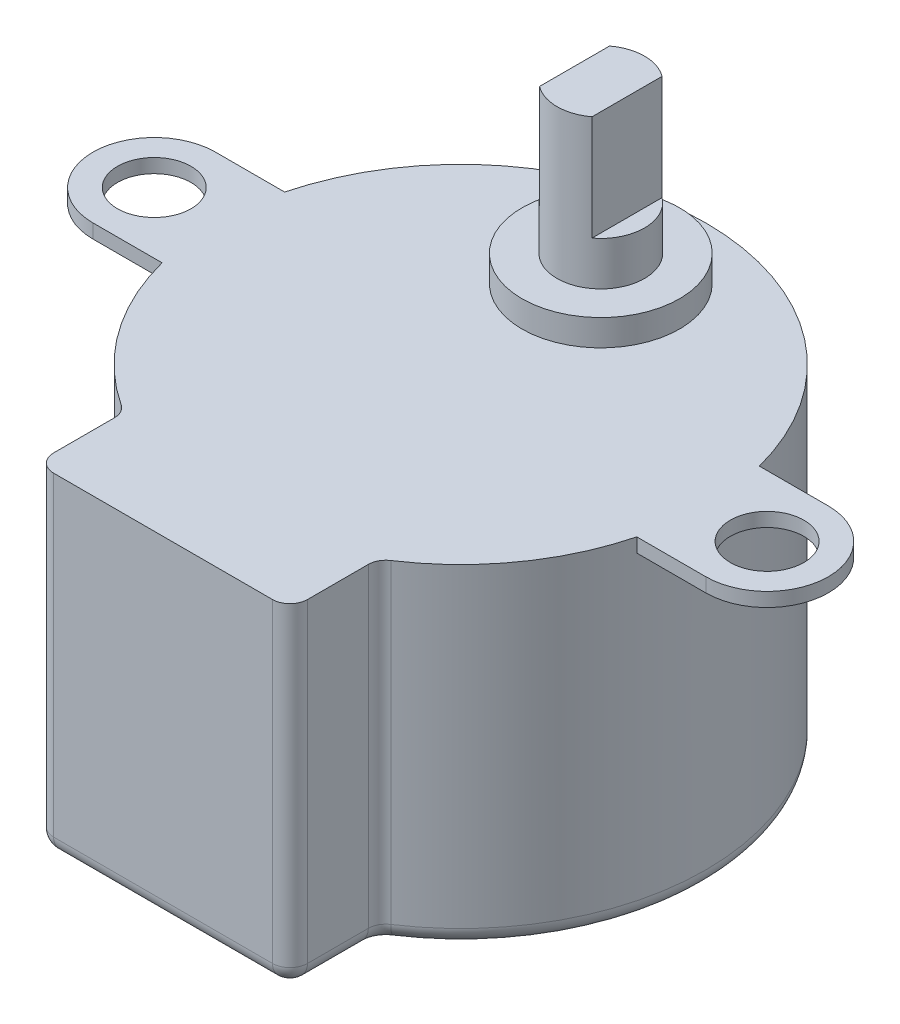
SolidWorks part; units mm, degrees
ref_plane "Front Plane" through (0, 0, 0) normal (0, 0, 1) x (1, 0, 0)
ref_plane "Top Plane" through (0, 0, 0) normal (0, 1, 0) x (1, 0, 0)
ref_plane "Right Plane" through (0, 0, 0) normal (1, 0, 0) x (0, 0, -1)
sketch "Sketch1" plane through (0, 0, 0) normal (0, 1, 0) x (1, 0, 0)
  line L1 (-7.25, 0) -> (7.25, 0)
  line L2 (-7.25, 0) -> (-7.25, -17)
  line L3 (-7.25, -17) -> (7.25, -17)
  line L4 (7.25, 0) -> (7.25, -17)
  circle A0 centre (0, 0) radius 14
  dimension "D1" = 28
  dimension "D2" = 14.5
  dimension "D3" = 7.25
  dimension "D4" = 17
extrude "Boss-Extrude1" add sketch "Sketch1" along normal blind 19 contours A0 | L3 L4 L1 L2
sketch "Sketch2" plane through (0, 19, 0) normal (0, 1, 0) x (1, 0, 0)
  line L0 (-7.25, -17) -> (7.25, -17) construction
  circle A0 centre (0, 8) radius 2.5
  circle A1 centre (0, 8) radius 4.5
  dimension "D1" = 9
  dimension "D2" = 5
  dimension "D3" = 25
extrude "Boss-Extrude2" add sketch "Sketch2" along normal blind 1.5 contours A1
extrude "Boss-Extrude3" add sketch "Sketch2<3>" along normal blind 10 contours A0
sketch "Sketch2<3>" plane through (0, 19, 0) normal (0, 1, 0) x (1, 0, 0) same geometry as "Sketch2"
sketch "Sketch3" plane through (0, 29, 0) normal (0, 1, 0) x (1, 0, 0)
  line L0 (-1.5, 10.0498) -> (-1.5, 5.9502)
  line L1 (1.5, 10.0498) -> (1.5, 5.9502)
  circle A0 centre (0, 8) radius 2.54
  circle M1 centre (0, 8) radius 2.5
  dimension "D3" = 5.08
  dimension "D1" = 3
  dimension "D2" = 1.5
extrude "Cut-Extrude1" cut sketch "Sketch3" against normal blind 6 contours L0 M1 | L1 M1 region at (-1.9078, 29, -8) region at (1.9078, 29, -8)
fillet "Fillet1" radius 1 8 edges at (-7.25, 0, 14.4883) (0, 0, 17) (7.25, 0, 14.4883) (0, 0, -14) (7.25, 9.5, 11.9765) (-7.25, 9.5, 11.9765) (-7.25, 9.5, 17) (7.25, 9.5, 17)
sketch "Sketch4" plane through (0, 19, 0) normal (0, 1, 0) x (1, 0, 0)
  line L0 (-17.5023, 0) -> (17.4977, 0) construction
  line L1 (-17.5023, 3.5) -> (17.4977, 3.5)
  line L2 (-17.5023, -3.5) -> (17.4977, -3.5)
  circle A0 centre (17.4977, 0) radius 2.1
  circle A1 centre (-17.5023, 0) radius 2.1
  arc A2 (-17.5023, 3.5) -> (-17.5023, -3.5) centre (-17.5023, 0) ccw
  arc A3 (17.4977, -3.5) -> (17.4977, 3.5) centre (17.4977, 0) ccw
  circle A4 centre (0, 8) radius 4.5 construction
  point P4 (-0.0023, 0)
  dimension "D2" = 4.2
  dimension "D3" = 4.2
  dimension "D4" = 8
  dimension "D1" = 35
  dimension "D5" = 7
extrude "Boss-Extrude4" add sketch "Sketch4" against normal blind 0.8
